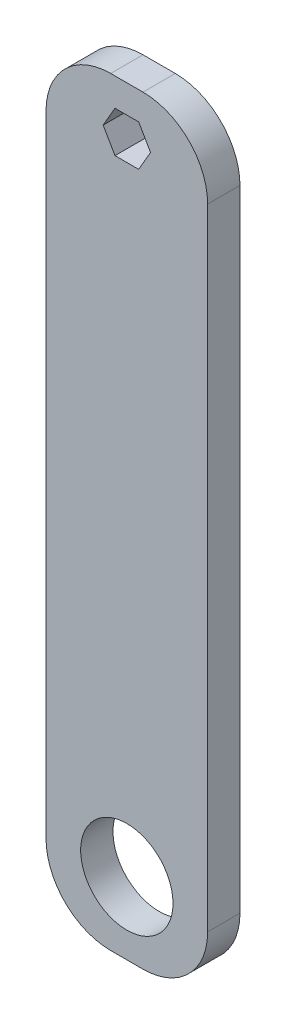
SolidWorks part; units mm, degrees
ref_plane "Front Plane" through (0, 0, 0) normal (0, 0, 1) x (1, 0, 0)
ref_plane "Top Plane" through (0, 0, 0) normal (0, 1, 0) x (1, 0, 0)
ref_plane "Right Plane" through (0, 0, 0) normal (1, 0, 0) x (0, 0, -1)
sketch "Sketch1" plane through (0, 0, 0) normal (0, 1, 0) x (1, 0, 0)
  line L1 (-25, -5) -> (25, -5)
  line L2 (-25, -5) -> (-25, 5)
  line L3 (-25, 5) -> (25, 5)
  line L4 (25, -5) -> (25, 5)
  line L5 (-25, -5) -> (25, 5) construction
  line L6 (-25, 5) -> (25, -5) construction
  point P0 (0, 0)
  dimension "D1" = 50
  dimension "D2" = 10
extrude "Boss-Extrude1" add sketch "Sketch1" along normal mid plane 235
ref_plane "Plane1" through (0, 102.5, 0) normal (0, 1, 0) x (1, 0, 0)
sketch "Sketch2" plane through (0, 0, 5) normal (0, 0, 1) x (1, 0, 0)
  line L0 (0, -55) -> (0, 55) construction
  line L1 (5.5, 102.5) -> (-5.5, 102.5) construction
  line L2 (3.6662, 96.15) -> (7.3323, 102.5)
  line L3 (7.3323, 102.5) -> (3.6662, 108.85)
  line L4 (3.6662, 108.85) -> (-3.6662, 108.85)
  line L5 (-3.6662, 108.85) -> (-7.3323, 102.5)
  line L6 (-7.3323, 102.5) -> (-3.6662, 96.15)
  line L9 (-3.6662, 96.15) -> (3.6662, 96.15)
  circle A0 centre (0, 102.5) radius 6.35 construction
  circle A2 centre (0, -95.25) radius 14.2875
  dimension "D1" = 12.7
  dimension "D2" = 197.75
  dimension "D3" = 28.575
extrude "Cut-Extrude1" cut sketch "Sketch2" against normal blind 127
fillet "Fillet1" radius 20 4 edges at (-25, -117.5, 0) (25, -117.5, 0) (25, 117.5, 0) (-25, 117.5, 0)
ref_axis "Axis1" through (0, -95.25, -5) along (0, 0, 1)
ref_axis "Axis2" through (0, 102.5, -88.99) along (0, 0, 1)
